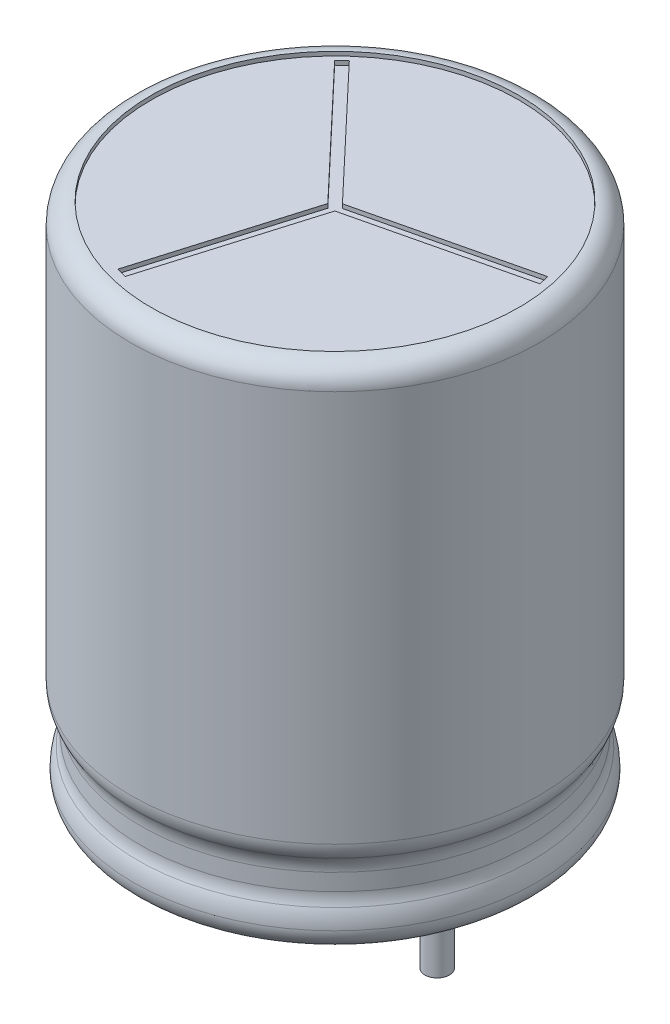
SolidWorks part; units mm, degrees
ref_plane "Front Plane" through (0, 0, 0) normal (0, 0, 1) x (1, 0, 0)
ref_plane "Top Plane" through (0, 0, 0) normal (0, 1, 0) x (1, 0, 0)
ref_plane "Right Plane" through (0, 0, 0) normal (1, 0, 0) x (0, 0, -1)
sketch "Sketch1" plane through (0, 0, 0) normal (0, 0, 1) x (1, 0, 0)
  line L0 (5, 12.5) -> (0, 12.5)
  line L1 (0, 12.5) -> (0, 0)
  line L2 (0, 0) -> (4.8272, 0)
  line L3 (4.7604, 1.2326) -> (4.7604, 1.6424)
  line L4 (5, 2.4076) -> (5, 12.5)
  line L5 (0, 12.5) -> (0, 0) construction
  arc A0 (4.8272, 0) -> (4.8262, 0.9429) centre (3.8389, 0.4704) ccw
  arc A1 (4.8262, 0.9429) -> (4.7604, 1.2326) centre (5.4312, 1.2326) cw
  arc A2 (4.7604, 1.6424) -> (4.8802, 2.025) centre (5.4313, 1.6424) cw
  arc A3 (4.8802, 2.025) -> (5, 2.4076) centre (4.3292, 2.4076) ccw
  point P14 (0, 0)
  point P15 (0, 0)
  point P16 (4.8262, 0)
  dimension "D1" = 12.5
  dimension "D2" = 5
revolve "Revolve1" add sketch "Sketch1" angle 360 about L5 reverse direction yes
sketch "Sketch2" plane through (0, 12.5, 0) normal (0, 1, 0) x (-1, 0, 0)
  circle A0 centre (0, 0) radius 4.5
  dimension "D1" = 9
extrude "Cut-Extrude1" cut sketch "Sketch2" against normal blind 0.1
sketch "Sketch3" plane through (0, 12.4, 0) normal (0, 1, 0) x (-1, 0, 0)
  line L0 (2.906, -3.2561) -> (3.0905, -3.0815)
  line L1 (3.0905, -3.0815) -> (0.1426, 0.034)
  line L2 (0.1426, 0.034) -> (1.3206, 3.9896)
  line L3 (1.3206, 3.9896) -> (1.0772, 4.0621)
  line L4 (1.0772, 4.0621) -> (-0.1008, 0.1065)
  line L5 (-0.1008, 0.1065) -> (-4.1556, -0.8607)
  line L6 (-4.1556, -0.8607) -> (-4.0967, -1.1077)
  line L7 (-4.0967, -1.1077) -> (-0.0419, -0.1405)
  line L8 (-0.0419, -0.1405) -> (2.906, -3.2561)
extrude "Cut-Extrude2" cut sketch "Sketch3" against normal blind 0.1
ref_plane "Plane1" through (0, 0, 0) normal (0, 0, -1) x (-1, 0, 0)
sketch "Sketch4" plane through (0, 0, 0) normal (0, 0, -1) x (-1, 0, 0)
  line L0 (-2.8, -2.5) -> (-2.5, -2.5)
  line L1 (-2.5, -2.5) -> (-2.5, 0)
  line L2 (-2.5, 0) -> (-2.8, 0)
  line L3 (-2.8, 0) -> (-2.8, -2.5)
  line L4 (-2.5, -2.5) -> (-2.5, 0) construction
  dimension "D1" = 2.5
revolve "Revolve2" add sketch "Sketch4" angle 360 about L4 reverse direction yes
fillet "Fillet1" radius 0.5 2 edges at (0, 12.5, -5) (0, 0, -4.8272) tangent propagation no
mirror "Simetría3" about plane through (0, 0, 0) normal (1, 0, 0) of "Revolve2"
